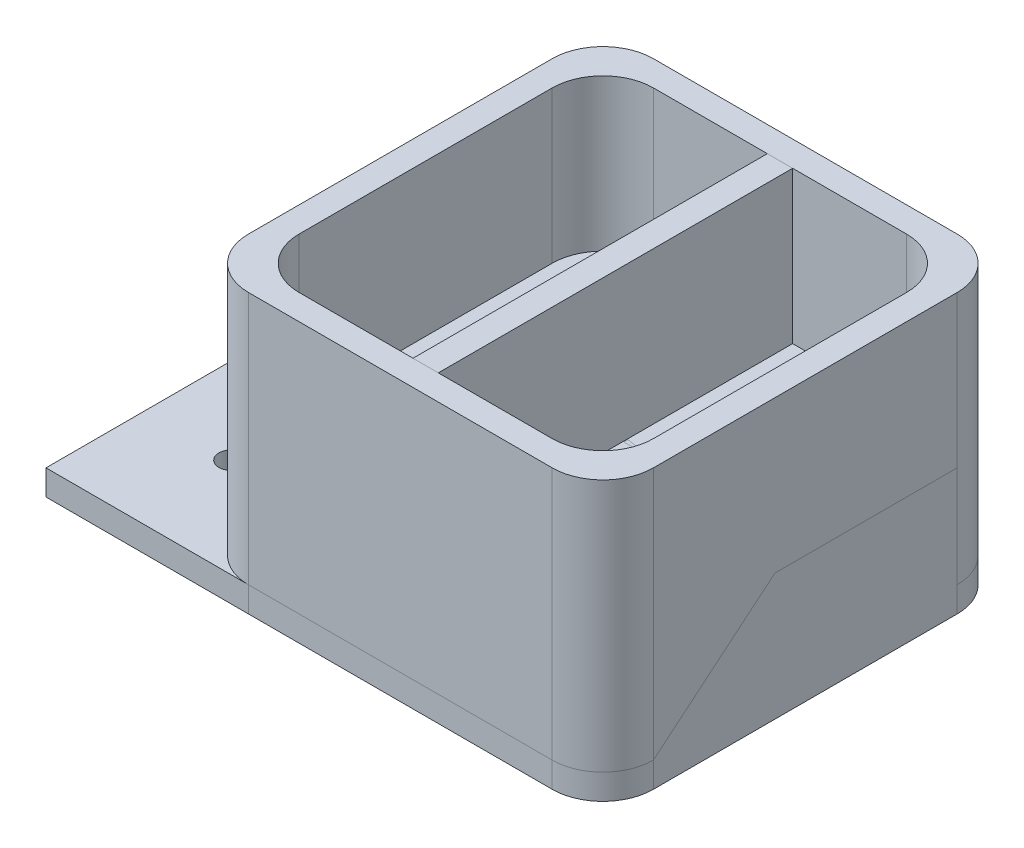
SolidWorks part; units mm, degrees
ref_plane "Front Plane" through (0, 0, 0) normal (0, 0, 1) x (1, 0, 0)
ref_plane "Top Plane" through (0, 0, 0) normal (0, 1, 0) x (1, 0, 0)
ref_plane "Right Plane" through (0, 0, 0) normal (1, 0, 0) x (0, 0, -1)
sketch "Sketch2" plane through (0, 0, 0) normal (0, 1, 0) x (1, 0, 0)
  line L0 (32.5, 35) -> (32.5, 70)
  line L1 (10, 0) -> (60, 0)
  line L2 (0, 10) -> (0, 60)
  line L3 (10, 70) -> (60, 70)
  line L4 (70, 10) -> (70, 60)
  line L9 (5, 75) -> (-35, 75)
  line L10 (32.5, 70) -> (37.5, 70)
  line L11 (37.5, 70) -> (37.5, 0)
  line L12 (37.5, 0) -> (32.5, 0)
  line L13 (32.5, 0) -> (32.5, 35)
  line L14 (65, 75) -> (5, 75)
  line L15 (75, 65) -> (75, 5)
  line L16 (65, -5) -> (5, -5)
  line L17 (-5, 65) -> (-5, 5)
  line L18 (-35, 75) -> (-35, -5)
  line L19 (-35, -5) -> (5, -5)
  arc A0 (10, 0) -> (0, 10) centre (10, 10) cw
  arc A1 (60, 0) -> (70, 10) centre (60, 10) ccw
  arc A2 (60, 70) -> (70, 60) centre (60, 60) cw
  arc A3 (0, 60) -> (10, 70) centre (10, 60) cw
  circle A4 centre (17.5, 35) radius 15
  circle A5 centre (17.5, 35) radius 8.5
  circle A8 centre (52.5, 35) radius 8.5
  circle A9 centre (52.5, 35) radius 15
  arc A10 (75, 5) -> (65, -5) centre (65, 5) cw
  arc A11 (5, -5) -> (-5, 5) centre (5, 5) cw
  arc A12 (5, 75) -> (-5, 65) centre (5, 65) ccw
  arc A13 (65, 75) -> (75, 65) centre (65, 65) cw
  circle A14 centre (-17.9776, 55) radius 2.5
  circle A15 centre (-17.9776, 14.6446) radius 2.5
  circle A16 centre (17.5, 35) radius 2.5
  circle A17 centre (52.5, 35) radius 2.5
  point P7 (0, 0)
  point P37 (35, 35)
  dimension "D1" = 10
  dimension "D2" = 10
extrude "Boss-Extrude1" add sketch "Sketch2" along normal blind 50 contours L14 A12 L17 A11 L16 A10 L15 L4 A1 L1 A0 L2 A3 L3 | A13 L14 L3 A2 L4 L15 region at (35, 0, -73.8686)
extrude "Boss-Extrude3" add sketch "Sketch2<5>" along normal blind 50 separate body contours L13 L1 L11 L3 L0 region at (35, 0, -35)
sketch "Sketch2<5>" plane through (0, 0, 0) normal (0, 1, 0) x (1, 0, 0) same geometry as "Sketch2"
extrude "Boss-Extrude4" add sketch "Sketch2<6>" along normal blind 20 separate body contours A9 A8 | A4 A5 region at (2.9243, 0, -35) region at (52.5, 0, -49.5757)
sketch "Sketch2<6>" plane through (0, 0, 0) normal (0, 1, 0) x (1, 0, 0) same geometry as "Sketch2"
extrude "Boss-Extrude5" add sketch "Sketch2<7>" along normal blind 20 and the other way blind 5 separate body contours A13 L14 A12 L17 A11 L16 A10 L15 L2 A3 L3 A2 L4 A1 L1 A0 | L13 A4 L0 L3 A3 L2 A0 L1 | A9 A8 | A8 | L13 L1 L11 L3 L0 | A5 | A4 A5 | L11 A9 L1 A1 L4 A2 L3 region at (31.7282, 0, -17.5) region at (35, 0, -35) region at (2.9243, 0, -35) region at (52.5, 0, -49.5757) region at (48.75, 0, -69.2282) region at (35, 0, -73.8686) region at (9.2404, 0, -35) region at (44.2404, 0, -35)
sketch "Sketch2<7>" plane through (0, 0, 0) normal (0, 1, 0) x (1, 0, 0) same geometry as "Sketch2"
extrude "Boss-Extrude6" add sketch "Sketch2<8>" against normal blind 5 separate body contours A12 L9 L18 L19 A11 L17 A15 A14 region at (-19.7253, 0, -35.0029)
sketch "Sketch2<8>" plane through (0, 0, 0) normal (0, 1, 0) x (1, 0, 0) same geometry as "Sketch2"
